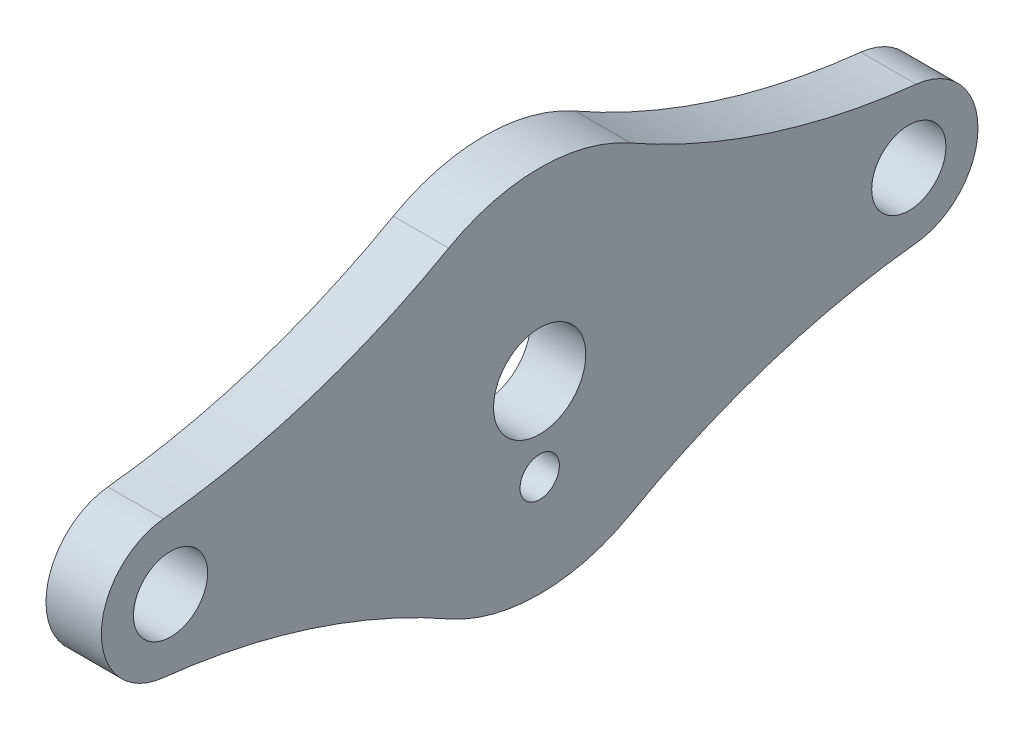
SolidWorks part; units mm, degrees
material "PET"
ref_plane "Front" through (0, 0, 0) normal (0, 0, 1) x (1, 0, 0)
ref_plane "Top" through (0, 0, 0) normal (0, 1, 0) x (1, 0, 0)
ref_plane "Right" through (0, 0, 0) normal (1, 0, 0) x (0, 0, -1)
sketch "Sketch1" plane through (0, 0, 0) normal (1, 0, 0) x (0, 0, -1)
  line L0 (0, 0) -> (0, 5.645) construction
  arc A0 (-25.906, 4.7355) -> (-25.906, -4.7355) centre (-25.4, 0) ccw
  circle A2 centre (0, 0) radius 25.4 construction
  arc A3 (-6.2607, -11.0496) -> (6.2607, -11.0496) centre (0, 0) ccw
  arc A4 (-25.906, 4.7355) -> (-6.2607, 11.0496) centre (-31.3035, 55.248) ccw
  arc A5 (-25.906, -4.7355) -> (-6.2607, -11.0496) centre (-31.3035, -55.248) cw
  arc A6 (25.906, -4.7355) -> (6.2607, -11.0496) centre (31.3035, -55.248) ccw
  arc A7 (25.906, 4.7355) -> (6.2607, 11.0496) centre (31.3035, 55.248) cw
  arc A8 (25.906, 4.7355) -> (25.906, -4.7355) centre (25.4, 0) cw
  arc A9 (6.2607, 11.0496) -> (-6.2607, 11.0496) centre (0, 0) ccw
  dimension "D1" = 50.8
  dimension "D2" = 9.525
  dimension "D3" = 25.4
  dimension "D4" = 50.8
extrude "Boss-Extrude1" add sketch "Sketch1" against normal blind 3.81
hole_wizard "#10 Clearance Hole1" positions "Sketch2" profile "Sketch3" hole size "#10" standard "ANSI Inch" end condition through all
sketch "Sketch2" plane through (-3.81, 0, 0) normal (-1, 0, 0) x (0, 0, 1)
  point P0 (-25.4, 0)
  point P3 (25.4, 0)
sketch "Sketch3" plane through (-3.81, 0, -25.4) normal (0, 1, 0) x (0, 0, 1)
  line L0 (0, 0) -> (0, 3.81)
  line L1 (0, 3.81) -> (2.5527, 3.81)
  line L2 (2.5527, 3.81) -> (2.5527, 0)
  line L5 (2.5527, 0) -> (0, 0)
  line L11 (0, -6.35) -> (0, 107.95) construction
  dimension "Thru Hole Dia." = 5.1054
  dimension "Thru Hole Depth" = 3.81
hole_wizard "#6-32 Tapped Hole1" positions "Sketch5" profile "Sketch6" tap size "#6-32" standard "ANSI Inch" end condition through all
sketch "Sketch5" plane through (-3.81, 0, 0) normal (-1, 0, 0) x (0, 0, 1)
  point P0 (0, -5.715)
  dimension "D1" = 5.715
sketch "Sketch6" plane through (-3.81, -5.715, 0) normal (0, 1, 0) x (0, 0, 1)
  line L0 (0, 0) -> (0, 3.81)
  line L1 (0, 3.81) -> (1.3525, 3.81)
  line L2 (1.3525, 3.81) -> (1.3525, 0)
  line L5 (1.3525, 0) -> (0, 0)
  line L11 (0, -6.35) -> (0, 107.95) construction
  dimension "Thru Tap Drill Dia." = 2.7051
  dimension "Thru Tap Drill Depth" = 3.81
cosmetic thread "Hole Thread1" parameters "D2"=3.5052
sketch "Sketch4" plane through (-3.81, 0, 0) normal (-1, 0, 0) x (0, 0, 1)
  circle A0 centre (0, 0) radius 3.175
  dimension "D1" = 6.35
extrude "Cut-Extrude1" cut sketch "Sketch4" against normal through all
